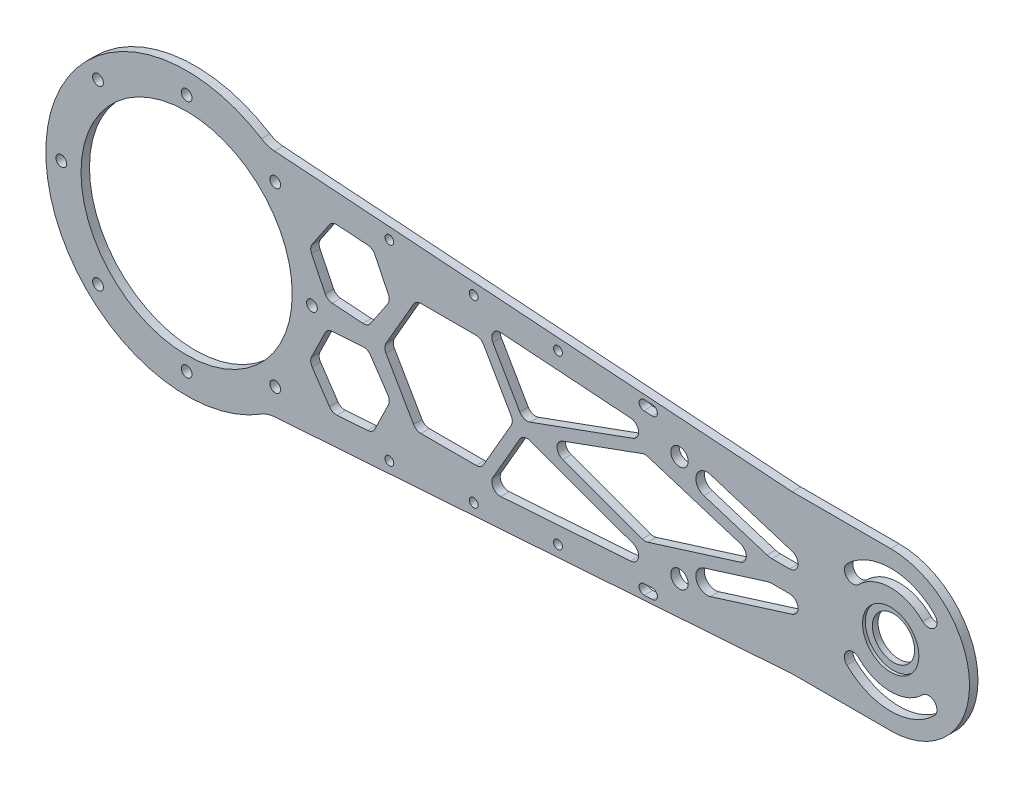
SolidWorks part; units mm, degrees
ref_plane "前视基准面" through (0, 0, 0) normal (0, 0, 1) x (1, 0, 0)
ref_plane "上视基准面" through (0, 0, 0) normal (0, 1, 0) x (1, 0, 0)
ref_plane "右视基准面" through (0, 0, 0) normal (1, 0, 0) x (0, 0, -1)
other "Configuration Table"
sketch "草图1" plane through (0, 0, 0) normal (0, 0, 1) x (1, 0, 0)
  line L0 (-54.9773, 0) -> (414.3888, 0) construction
  line L1 (250, 28) -> (215.3492, 28)
  line L7 (0, 0) -> (68.3787, 68.3787) construction
  line L11 (0, 23.45) -> (44.1599, 23.45) construction
  line L13 (0, -23.45) -> (230.55, -23.45) construction
  line L19 (214.6516, 28.0244) -> (31.1831, 40.8537)
  line L20 (0, -23.45) -> (44.1599, -23.45) construction
  line L24 (0, -23.45) -> (44.1599, -23.45) construction
  line L25 (215.6984, -28) -> (215, -28)
  line L26 (213.9134, -28.076) -> (215, -28)
  line L27 (214.6516, -28.0244) -> (31.1831, -40.8537)
  line L28 (213.9134, 28.076) -> (215, 28)
  line L29 (215.6984, 28) -> (215, 28)
  line L30 (250, -28) -> (215.3492, -28)
  arc A0 (35.445, 23.45) -> (42.5, 0) centre (0, 0) ccw construction
  arc A1 (0, 50) -> (0, -50) centre (0, 0) ccw
  arc A2 (250, -28) -> (250, 28) centre (250, 0) ccw
  circle A13 centre (0, 0) radius 23.45 construction
  arc A26 (215.3492, 28) -> (214.6516, 28.0244) centre (215.3492, 38) cw
  arc A27 (26.5672, 42.3578) -> (26.5672, -42.3578) centre (0, 0) ccw
  arc A28 (31.1831, -40.8537) -> (26.5672, -42.3578) centre (31.8806, -50.8294) ccw
  arc A30 (31.1831, 40.8537) -> (26.5672, 42.3578) centre (31.8806, 50.8294) cw
  arc A31 (215.3492, -28) -> (214.6516, -28.0244) centre (215.3492, -38) ccw
  point P17 (35, 50)
  point P19 (35.3553, 35.3553)
  point P22 (235, -19)
  point P27 (35, -50)
  point P30 (35.3553, -35.3553)
  point P35 (35.3553, 35.3553)
  point P39 (215, 28)
  point P40 (29.0913, -41)
  point P46 (29.0913, 41)
  dimension "D1" = 85
  dimension "D2" = 100
  dimension "D3" = 250
  dimension "D4" = 56
  dimension "D7" = 46.9
  dimension "D10" = 4
  dimension "D9" = 10
  dimension "D5" = 35
  dimension "D6" = 35
  dimension "D8" = 45
extrude "凸台-拉伸1" add sketch "草图1" along normal blind 3 contours A2 L1 A1 region at (98.0515, 0, 0)
sketch "草图2" plane through (0, 0, 3) normal (0, 0, 1) x (1, 0, 0)
  line L0 (0, 42.5) -> (0, 0) construction
  line L1 (0, 0) -> (30.052, 30.052) construction
  line L2 (0, 0) -> (30.052, -30.052) construction
  line L3 (0, 0) -> (-30.052, -30.052) construction
  line L4 (-30.052, 30.052) -> (0, 0) construction
  circle A0 centre (0, 0) radius 44.5 construction
  circle A1 centre (0, 0) radius 42.5 construction
  circle A3 centre (-30.052, 30.052) radius 1.6
  circle A5 centre (30.052, 30.052) radius 1.6
  circle A7 centre (30.052, -30.052) radius 1.6
  circle A9 centre (-30.052, -30.052) radius 1.6
  circle A10 centre (-42.5, 0) radius 1.6
  circle A11 centre (42.5, 0) radius 1.6
  circle A14 centre (0, 0) radius 37.5
  circle A15 centre (0, 44.5) radius 1.9
  circle A17 centre (0, 42.5) radius 1.9
  circle A18 centre (0, -42.5) radius 1.9
  circle A19 centre (31.4663, 31.4663) radius 1.9
  circle A20 centre (44.5, 0) radius 1.9
  circle A21 centre (31.4663, -31.4663) radius 1.9
  circle A22 centre (0, -44.5) radius 1.9
  circle A23 centre (-31.4663, -31.4663) radius 1.9
  circle A24 centre (-44.5, 0) radius 1.9
  circle A25 centre (-31.4663, 31.4663) radius 1.9
  point P23 (0, 0)
  point P43 (0, 0)
  dimension "D1" = 89
  dimension "D2" = 85
  dimension "D3" = 3.8
  dimension "D5" = 3.2
  dimension "D6" = 3.2
  dimension "D7" = 75
  dimension "D8" = 3.2
  dimension "D9" = 3.2
  dimension "D10" = 3.2
  dimension "D11" = 3.2
  dimension "D12" = 3.8
  dimension "D13" = 3.8
  dimension "D14" = 45
  dimension "D15" = 45
  dimension "D16" = 45
  dimension "D17" = 45
  dimension "D19" = 45
  dimension "D18" = 8
sketch "草图3" plane through (0, 0, 3) normal (0, 0, 1) x (1, 0, 0)
  circle A0 centre (250, 0) radius 7.5
  dimension "D1" = 15
extrude "切除-拉伸2" cut sketch "草图3" against normal blind 10
sketch "草图4" plane through (0, 0, 3) normal (0, 0, 1) x (1, 0, 0)
  circle A0 centre (250, 0) radius 10
  dimension "D1" = 20
extrude "切除-拉伸3" cut sketch "草图4" against normal blind 1
sketch "草图5" plane through (0, 0, 3) normal (0, 0, 1) x (1, 0, 0)
  line L0 (48.4847, 35.6341) -> (223.0476, 23.4275) construction
  line L1 (215, 28) -> (31.1831, 40.8537) construction
  line L2 (-65.6151, 0) -> (287.8163, 0) construction
  circle A0 centre (72, 33.9898) radius 1.55
  circle A1 centre (101.9269, 31.8971) radius 1.55
  circle A2 centre (131.8538, 29.8044) radius 1.55
  circle A4 centre (131.8538, -29.8044) radius 1.55
  circle A5 centre (101.9269, -31.8971) radius 1.55
  circle A6 centre (72, -33.9898) radius 1.55
  dimension "D2" = 3.1
  dimension "D4" = 30
  dimension "D5" = 30
  dimension "D1" = 4
  dimension "D3" = 72
extrude "切除-拉伸4" cut sketch "草图5" against normal blind 10
sketch "草图6" plane through (0, 0, 3) normal (0, 0, 1) x (1, 0, 0)
  line L0 (175, 58.714) -> (175, -75.5395) construction
  line L1 (250, -28) -> (215, -28) construction
  line L2 (0, 0) -> (337.5517, 0) construction
  circle A0 centre (250, 0) radius 7.5 construction
  circle A1 centre (175, -21) radius 3.1
  circle A2 centre (175, 21) radius 3.1
  dimension "D2" = 6.2
  dimension "D3" = 7
  dimension "D1" = 75
extrude "切除-拉伸5" cut sketch "草图6" against normal blind 10
sketch "草图8" plane through (0, 0, 3) normal (0, 0, 1) x (1, 0, 0)
  line L0 (224.4479, 0) -> (275.1584, 0) construction
  line L1 (236.565, 13.435) -> (250, 0) construction
  line L2 (250, 0) -> (263.435, 13.435) construction
  circle A0 centre (250, 0) radius 16
  circle A1 centre (250, 0) radius 22
  circle A2 centre (250, 0) radius 19 construction
  circle A3 centre (236.565, 13.435) radius 3
  circle A5 centre (263.435, 13.435) radius 3
  circle A7 centre (263.435, -13.435) radius 3
  circle A8 centre (236.565, -13.435) radius 3
  line M31 (31.1831, -40.8537) -> (215, -28)
  dimension "D1" = 32
  dimension "D2" = 44
  dimension "D3" = 38
  dimension "D4" = 45
  dimension "D5" = 90
extrude "切除-拉伸7" cut sketch "草图8" against normal blind 9 contours A3 | A5 A1 A3 A0 | A5 | A8 | A0 A8 A1 A7 | A7 M31 region at (250, 17.7943, 3) region at (263.435, 13.435, 3) region at (250, -17.7943, 3) region at (263.435, -13.435, 3) region at (236.565, 13.435, 3) region at (236.565, -13.435, 3)
sketch "草图9" plane through (0, 0, 3) normal (0, 0, 1) x (1, 0, 0)
  line L0 (175, 21) -> (175, 5) construction
  line L1 (178.1, 21) -> (178.1, 5)
  line L2 (171.9, 21) -> (171.9, 5)
  arc A0 (178.1, 21) -> (171.9, 21) centre (175, 21) ccw
  arc A1 (171.9, 5) -> (178.1, 5) centre (175, 5) ccw
  circle A2 centre (175, 21) radius 3.1 construction
  point P3 (175, 13)
  dimension "D1" = 16
extrude "切除-拉伸9" cut sketch "草图9" against normal blind 10
extrude "切除-拉伸12" cut sketch "草图2" against normal blind 10 contours A14 | A15 A17 | A15 A17 | A18 | A18 | A7 A21 | A7 A21 | A11 A20 | A11 A20 | A5 A19 | A5 A19 | A3 A25 | A3 A25 | A10 A24 | A10 A24 | A9 A23 | A9 A23 region at (-30.6429, 30.6429, 3) region at (-31.7626, 31.7626, 3) region at (30.6429, 30.6429, 3) region at (31.7626, 31.7626, 3) region at (30.6429, -30.6429, 3) region at (31.7626, -31.7626, 3) region at (-30.6429, -30.6429, 3) region at (-31.7626, -31.7626, 3) region at (-43.3356, 0, 3) region at (-44.9192, 0, 3) region at (43.3356, 0, 3) region at (44.9192, 0, 3) region at (0, 0, 3) region at (0, 43.5, 3) region at (0, 41.932, 3) region at (0, -41.932, 3) region at (0, -43.5, 3)
sketch "草图11" plane through (0, 0, 3) normal (0, 0, 1) x (1, 0, 0)
  line L0 (131.8538, 29.8044) -> (163.9169, 28.2643)
  line L1 (0, 0) -> (250, 0) construction
  line L2 (162.4186, 28.3362) -> (165.4151, 28.1923) construction
  line L4 (215, 28) -> (31.1831, 40.8537)
  line L6 (215, -28) -> (250, -28)
  line L7 (250, 28) -> (215, 28)
  line L10 (215, -28) -> (250, -28)
  line L11 (250, 28) -> (215, 28)
  line L13 (162.5026, 30.0842) -> (165.4991, 29.9403)
  line L14 (162.3346, 26.5882) -> (165.3312, 26.4443)
  line L15 (162.4186, -28.3362) -> (165.4151, -28.1923) construction
  line L16 (162.5026, -30.0842) -> (165.4991, -29.9403)
  line L17 (162.3346, -26.5882) -> (165.3312, -26.4443)
  line L22 (215, 28) -> (31.1831, 40.8537)
  line L24 (31.1831, -40.8537) -> (215, -28)
  line L25 (31.1831, -40.8537) -> (215, -28)
  circle A0 centre (131.8538, 29.8044) radius 1.55 construction
  circle A1 centre (131.8538, 29.8044) radius 1.55
  circle A2 centre (163.9169, 28.2643) radius 1.75
  circle A3 centre (163.9169, -28.2643) radius 1.75
  arc A4 (26.5672, 42.3578) -> (31.1831, 40.8537) centre (31.8806, 50.8294) ccw
  arc A5 (26.5672, 42.3578) -> (26.5672, -42.3578) centre (0, 0) ccw
  arc A6 (31.1831, -40.8537) -> (26.5672, -42.3578) centre (31.8806, -50.8294) ccw
  arc A7 (250, -28) -> (250, 28) centre (250, 0) ccw
  arc A8 (26.5672, 42.3578) -> (31.1831, 40.8537) centre (31.8806, 50.8294) ccw
  arc A9 (26.5672, 42.3578) -> (26.5672, -42.3578) centre (0, 0) ccw
  arc A10 (31.1831, -40.8537) -> (26.5672, -42.3578) centre (31.8806, -50.8294) ccw
  arc A11 (250, -28) -> (250, 28) centre (250, 0) ccw
  arc A14 (162.5026, 30.0842) -> (162.3346, 26.5882) centre (162.4186, 28.3362) ccw
  arc A15 (165.3312, 26.4443) -> (165.4991, 29.9403) centre (165.4151, 28.1923) ccw
  arc A16 (162.5026, -30.0842) -> (162.3346, -26.5882) centre (162.4186, -28.3362) cw
  arc A17 (165.3312, -26.4443) -> (165.4991, -29.9403) centre (165.4151, -28.1923) cw
  point P21 (163.9169, 28.2643)
  point P29 (163.9169, -28.2643)
  dimension "D2" = 3.5
  dimension "D5" = 1.75
  dimension "D3" = 32.1
  dimension "D6" = 3
  dimension "D1" = 0
extrude "切除-拉伸13" cut sketch "草图11" against normal blind 10 contours A2 | L14 A15 L13 A14 | L16 A17 L17 A16 region at (162.7735, 29.523, 3) body kept at (31.1831, -40.8537, 0)
sketch "草图12" plane through (0, 0, 3) normal (0, 0, 1) x (1, 0, 0)
  line L0 (178.1, 5) -> (178.1, 21) construction
  line L1 (171.9, 21) -> (171.9, 5) construction
  line L2 (178.1, 5) -> (178.1, 21)
  line L3 (171.9, 21) -> (171.9, 5)
  line L4 (0, 0) -> (250, 0) construction
  line L5 (171.9, -21) -> (171.9, -5)
  line L6 (178.1, -5) -> (178.1, -21)
  arc A0 (171.9, 5) -> (178.1, 5) centre (175, 5) ccw construction
  arc A1 (178.1, 21) -> (171.9, 21) centre (175, 21) ccw construction
  arc A2 (171.9, 5) -> (178.1, 5) centre (175, 5) ccw
  arc A3 (178.1, 21) -> (171.9, 21) centre (175, 21) ccw
  circle A4 centre (175, 18.8) radius 3.1
  circle A5 centre (175, -18.8) radius 3.1
  arc A6 (178.1, -21) -> (171.9, -21) centre (175, -21) cw
  arc A7 (171.9, -5) -> (178.1, -5) centre (175, -5) cw
  line M26 (178.1, 21) -> (178.1, 5)
  arc M27 (178.1, 5) -> (171.9, 5) centre (175, 5) cw
  line M28 (171.9, 5) -> (171.9, 21)
  arc M29 (171.9, 21) -> (178.1, 21) centre (175, 21) cw
  circle M34 centre (175, -21) radius 3.1
  dimension "D1" = 2.2
extrude "凸台-拉伸2" add sketch "草图12" against normal blind 3 contours A4 L2 M28 M27 | A4 L3 M26 M29 | A5 M34 region at (175, 9.4653, 3) region at (175, 22.3347, 3) region at (175, -22.388, 3)
extrude "切除-拉伸14" cut sketch "草图12<9>" against normal blind 10 contours A5 M34 region at (175, -17.412, 3)
sketch "草图12<9>" plane through (0, 0, 3) normal (0, 0, 1) x (1, 0, 0) same geometry as "草图12"
sketch "草图14" plane through (0, 0, 3) normal (0, 0, 1) x (1, 0, 0)
  line L0 (0, 0) -> (250, 0) construction
  line L1 (108.7523, 20.7161) -> (118.2996, 4.1798)
  line L2 (71.6393, 16.9735) -> (66.8305, 26.8329)
  line L3 (64.3434, 28.5105) -> (53.4005, 29.2757)
  line L4 (215, 28) -> (31.1831, 40.8537)
  line L6 (215, -28) -> (250, -28)
  line L7 (250, 28) -> (215, 28)
  line L10 (215, -28) -> (250, -28)
  line L11 (250, 28) -> (215, 28)
  line L12 (50.7041, 27.9606) -> (44.57, 18.8663)
  line L13 (44.3607, 15.8737) -> (49.1695, 6.0142)
  line L14 (51.6566, 4.3366) -> (62.5995, 3.5714)
  line L15 (65.2959, 4.8865) -> (71.43, 13.9808)
  line L16 (66.8305, -26.8329) -> (71.6393, -16.9735)
  line L17 (71.43, -13.9808) -> (65.2959, -4.8865)
  line L18 (62.5995, -3.5714) -> (51.6566, -4.3366)
  line L19 (49.1695, -6.0142) -> (44.3607, -15.8737)
  line L20 (44.57, -18.8663) -> (50.7041, -27.9606)
  line L21 (53.4005, -29.2757) -> (64.3434, -28.5105)
  line L22 (115.228, 1.5) -> (105.413, 18.5)
  line L23 (102.815, 20) -> (83.185, 20)
  line L24 (80.587, 18.5) -> (70.772, 1.5)
  line L25 (70.772, -1.5) -> (80.587, -18.5)
  line L26 (83.185, -20) -> (102.815, -20)
  line L27 (105.413, -18.5) -> (115.228, -1.5)
  line L28 (121.9235, 2.8607) -> (158.5044, 16.1714)
  line L29 (157.6879, 21.9832) -> (111.5597, 25.2088)
  line L30 (157.6879, -21.9832) -> (111.5597, -25.2088)
  line L31 (121.9235, -2.8607) -> (158.5044, -16.1714)
  line L32 (108.7523, -20.7161) -> (118.2996, -4.1798)
  line L33 (133.5075, 2.8192) -> (161.806, 13.1161)
  line L34 (163.7282, 13.1599) -> (196.6157, 2.863)
  line L35 (196.6157, -2.863) -> (163.7282, -13.1599)
  line L36 (161.806, -13.1161) -> (133.5075, -2.8192)
  line L37 (184.8181, 14.9397) -> (232.534, 0) construction
  line L38 (186.0133, 18.757) -> (233.7292, 3.8173)
  line L39 (183.623, 11.1224) -> (231.3388, -3.8173)
  line L40 (184.8181, -14.9397) -> (232.534, 0) construction
  line L41 (186.0133, -18.757) -> (233.7292, -3.8173)
  line L42 (183.623, -11.1224) -> (231.3388, 3.8173)
  line L43 (233.7292, 3.8173) -> (206.9549, 3.8173)
  line L44 (233.7292, -3.8173) -> (206.9549, -3.8173)
  line L49 (215, 28) -> (31.1831, 40.8537)
  line L51 (31.1831, -40.8537) -> (215, -28)
  line L52 (31.1831, -40.8537) -> (215, -28)
  circle A0 centre (58, 16.4236) radius 12.5 construction
  circle A1 centre (58, -16.4236) radius 12.5 construction
  circle A2 centre (93, 0) radius 20 construction
  arc A3 (186.0133, 18.757) -> (183.623, 11.1224) centre (184.8181, 14.9397) ccw
  arc A4 (26.5672, 42.3578) -> (31.1831, 40.8537) centre (31.8806, 50.8294) ccw
  arc A5 (26.5672, 42.3578) -> (26.5672, -42.3578) centre (0, 0) ccw
  arc A6 (31.1831, -40.8537) -> (26.5672, -42.3578) centre (31.8806, -50.8294) ccw
  arc A7 (250, -28) -> (250, 28) centre (250, 0) ccw
  arc A8 (26.5672, 42.3578) -> (31.1831, 40.8537) centre (31.8806, 50.8294) ccw
  arc A9 (26.5672, 42.3578) -> (26.5672, -42.3578) centre (0, 0) ccw
  arc A10 (31.1831, -40.8537) -> (26.5672, -42.3578) centre (31.8806, -50.8294) ccw
  arc A11 (250, -28) -> (250, 28) centre (250, 0) ccw
  arc A12 (233.7292, -3.8173) -> (233.7292, 3.8173) centre (232.534, 0) ccw
  arc A13 (186.0133, -18.757) -> (183.623, -11.1224) centre (184.8181, -14.9397) cw
  arc A14 (233.7292, 3.8173) -> (233.7292, -3.8173) centre (232.534, 0) cw
  arc A15 (196.6157, 2.863) -> (196.6157, -2.863) centre (195.7193, 0) cw
  arc A16 (163.7282, -13.1599) -> (161.806, -13.1161) centre (162.8318, -10.297) cw
  arc A17 (161.806, 13.1161) -> (163.7282, 13.1599) centre (162.8318, 10.297) cw
  arc A18 (133.5075, 2.8192) -> (133.5075, -2.8192) centre (134.5333, 0) ccw
  arc A19 (118.2996, 4.1798) -> (121.9235, 2.8607) centre (120.8977, 5.6798) ccw
  arc A20 (108.7523, 20.7161) -> (111.5597, 25.2088) centre (111.3504, 22.2161) cw
  arc A21 (158.5044, 16.1714) -> (157.6879, 21.9832) centre (157.4786, 18.9905) ccw
  arc A22 (157.6879, -21.9832) -> (158.5044, -16.1714) centre (157.4786, -18.9905) ccw
  arc A23 (121.9235, -2.8607) -> (118.2996, -4.1798) centre (120.8977, -5.6798) ccw
  arc A24 (111.5597, -25.2088) -> (108.7523, -20.7161) centre (111.3504, -22.2161) cw
  arc A25 (80.587, -18.5) -> (83.185, -20) centre (83.185, -17) ccw
  arc A26 (102.815, -20) -> (105.413, -18.5) centre (102.815, -17) ccw
  arc A27 (115.228, 1.5) -> (115.228, -1.5) centre (112.6299, 0) cw
  arc A28 (105.413, 18.5) -> (102.815, 20) centre (102.815, 17) ccw
  arc A29 (83.185, 20) -> (80.587, 18.5) centre (83.185, 17) ccw
  arc A30 (70.772, 1.5) -> (70.772, -1.5) centre (73.3701, 0) ccw
  arc A31 (71.6393, -16.9735) -> (71.43, -13.9808) centre (68.9429, -15.6584) ccw
  arc A32 (66.8305, -26.8329) -> (64.3434, -28.5105) centre (64.1342, -25.5178) cw
  arc A33 (50.7041, -27.9606) -> (53.4005, -29.2757) centre (53.1912, -26.283) ccw
  arc A34 (44.3607, -15.8737) -> (44.57, -18.8663) centre (47.0571, -17.1888) ccw
  arc A35 (51.6566, -4.3366) -> (49.1695, -6.0142) centre (51.8658, -7.3293) ccw
  arc A36 (65.2959, -4.8865) -> (62.5995, -3.5714) centre (62.8088, -6.5641) ccw
  arc A37 (44.57, 18.8663) -> (44.3607, 15.8737) centre (47.0571, 17.1888) ccw
  arc A38 (49.1695, 6.0142) -> (51.6566, 4.3366) centre (51.8658, 7.3293) ccw
  arc A39 (62.5995, 3.5714) -> (65.2959, 4.8865) centre (62.8088, 6.5641) ccw
  arc A40 (71.6393, 16.9735) -> (71.43, 13.9808) centre (68.9429, 15.6584) cw
  arc A41 (66.8305, 26.8329) -> (64.3434, 28.5105) centre (64.1342, 25.5178) ccw
  arc A42 (53.4005, 29.2757) -> (50.7041, 27.9606) centre (53.1912, 26.283) ccw
  point P49 (208.6761, 7.4698)
  point P56 (208.6761, -7.4698)
  point P66 (205.7597, 0)
  point P71 (162.7597, 13.4632)
  point P74 (125.7597, 0)
  point P77 (119.5581, 2)
  point P80 (105.9313, 25.6024)
  point P83 (171.7705, 20.9985)
  point P86 (171.7705, -20.9985)
  point P89 (119.5581, -2)
  point P92 (105.9313, -25.6024)
  dimension "D20" = 4
  dimension "D21" = 3
  dimension "D2" = 25
  dimension "D3" = 25
  dimension "D4" = 58
  dimension "D5" = 58
  dimension "D8" = 93
  dimension "D9" = 4
  dimension "D10" = 40
  dimension "D12" = 4
  dimension "D13" = 66
  dimension "D14" = 2
  dimension "D15" = 4
  dimension "D16" = 43
  dimension "D17" = 80
  dimension "D18" = 4
  dimension "D19" = 50
  dimension "D1" = 0
extrude "切除-拉伸15" cut sketch "草图14" against normal blind 10 contours L3 A42 L12 A37 L13 A38 L14 A39 L15 A40 L2 A41 | L17 A36 L18 A35 L19 A34 L20 A33 L21 A32 L16 A31 | L24 A30 L25 A25 L26 A26 L27 A27 L22 A28 L23 A29 | A24 L30 A22 L31 A23 L32 | L28 A21 L29 A20 L1 A19 | L33 A18 L36 A16 L35 A15 L34 A17 | L38 A3 L39 L43 | A13 L41 L44 L42 region at (131.3508, 15.9852, 3) region at (58, 16.4236, 3) region at (58, -16.4236, 3) region at (93, 0, 3) region at (131.3508, -15.9852, 3) region at (164.6212, 0, 3) region at (201.8408, 10.0521, 3) region at (201.8408, -10.0521, 3)
fillet "圆角1" radius 3 2 edges at (233.7292, -3.8173, 1.5) (233.7292, 3.8173, 1.5)
fillet "圆角2" radius 6 2 edges at (206.9549, -3.8173, 1.5) (206.9549, 3.8173, 1.5)
